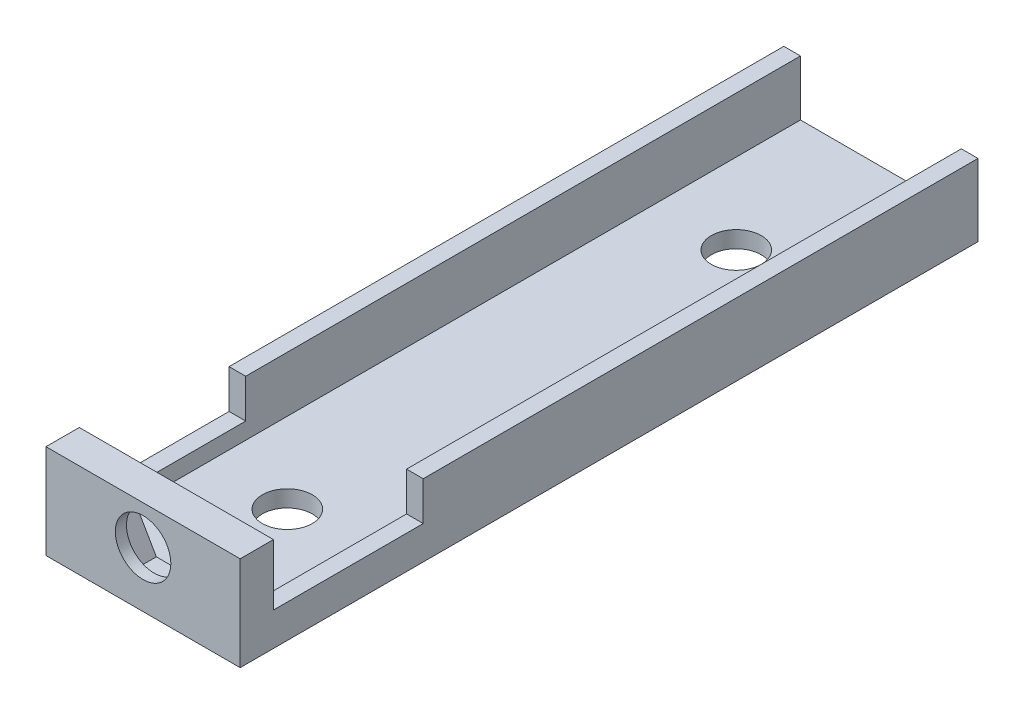
SolidWorks part; units mm, degrees
ref_plane "Front Plane" through (0, 0, 0) normal (0, 0, 1) x (1, 0, 0)
ref_plane "Top Plane" through (0, 0, 0) normal (0, 1, 0) x (1, 0, 0)
ref_plane "Right Plane" through (0, 0, 0) normal (1, 0, 0) x (0, 0, -1)
sketch "Sketch1" plane through (0, 0, 0) normal (0, 0, 1) x (1, 0, 0)
  line L0 (0, 0) -> (0, 13)
  line L1 (0, 13) -> (3, 13)
  line L2 (3, 13) -> (3, 3)
  line L3 (3, 3) -> (32, 3)
  line L4 (32, 3) -> (32, 13)
  line L5 (32, 13) -> (35, 13)
  line L6 (35, 13) -> (35, 0)
  line L7 (35, 0) -> (0, 0)
  line L8 (3, 3) -> (3, 0) construction
  dimension "D1" = 29
  dimension "D2" = 3
  dimension "D3" = 13
extrude "Boss-Extrude1" add sketch "Sketch1" along normal blind 100
sketch "Sketch2" plane through (0, 0, 100) normal (0, 0, 1) x (1, 0, 0)
  line L0 (3, 6) -> (3, 3)
  line L1 (3, 3) -> (3, 13) construction
  line L2 (3, 3) -> (32, 3)
  line L3 (32, 3) -> (32, 6)
  line L4 (32, 13) -> (32, 3) construction
  line L5 (32, 6) -> (35, 6)
  line L6 (35, 0) -> (35, 13) construction
  line L7 (35, 6) -> (35, 0)
  line L8 (35, 0) -> (0, 0)
  line L9 (0, 0) -> (0, 6)
  line L10 (0, 13) -> (0, 0) construction
  line L11 (0, 6) -> (3, 6)
  dimension "D1" = 3
extrude "Boss-Extrude2" add sketch "Sketch2" along normal blind 31
sketch "Sketch3" plane through (0, 0, 131) normal (0, 0, 1) x (1, 0, 0)
  line L0 (17.5, 10) -> (17.5, 17) construction
  line L1 (0, 0) -> (35, 0)
  line L2 (0, 0) -> (0, 17)
  line L3 (0, 17) -> (35, 17)
  line L4 (35, 0) -> (35, 17)
  line L5 (17.5, 10) -> (0, 10) construction
  line L6 (32, 3) -> (3, 3) construction
  line L8 (24.7169, 10) -> (21.1084, 16.25)
  line L9 (21.1084, 16.25) -> (13.8916, 16.25)
  line L10 (13.8916, 16.25) -> (10.2831, 10)
  line L11 (10.2831, 10) -> (13.8916, 3.75)
  line L12 (13.8916, 3.75) -> (21.1084, 3.75)
  line L13 (21.1084, 3.75) -> (24.7169, 10)
  circle A0 centre (17.5, 10) radius 5
  circle A1 centre (17.5, 10) radius 6.25 construction
  point P13 (24.7169, 9.5)
  point P21 (24.7169, 9.5)
  line M2 (3, 6) -> (0, 6)
  line M3 (0, 6) -> (0, 0)
  line M4 (0, 0) -> (35, 0)
  line M5 (35, 0) -> (35, 6)
  line M6 (35, 6) -> (32, 6)
  line M7 (32, 6) -> (32, 3)
  line M8 (32, 3) -> (3, 3)
  line M9 (3, 3) -> (3, 6)
  dimension "D1" = 10
  dimension "D2" = 17
  dimension "D3" = 12.5
extrude "Boss-Extrude3" add sketch "Sketch3" against normal blind 4 contours L4 L3 L2 L13 L12 L11 L10 L9 L8 M6 M2 M9 M8 M7 | M9 M2 M3 M4 M5 M6 M7 M8 region at (17.5, 1.939, 131) region at (0.377, 11.5, 131)
sketch "Sketch4" plane through (0, 3, 0) normal (0, 1, 0) x (1, 0, 0)
  line L0 (17.5, -26.075) -> (17.5, -107) construction
  line L1 (32, -127) -> (32, 0) construction
  line L2 (3, -127) -> (3, 0) construction
  line L4 (32, -127) -> (3, -127) construction
  circle A0 centre (17.5, -107) radius 4.5
  circle A1 centre (17.5, -26.075) radius 4.5
  dimension "D1" = 9
  dimension "D2" = 20
  dimension "D3" = 80.925
extrude "Cut-Extrude1" cut sketch "Sketch4" against normal through all
extrude "Boss-Extrude4" add sketch "Sketch3<4>" along normal blind 2 contours L4 L3 L2 L13 L12 L11 L10 L9 L8 M6 M2 M9 M8 M7 | M9 M2 M3 M4 M5 M6 M7 M8 | L12 L13 L8 L9 L10 L11 A0 region at (17.5, 1.939, 131) region at (0.377, 11.5, 131) region at (22.7473, 6.9705, 131)
sketch "Sketch3<4>" plane through (0, 0, 131) normal (0, 0, 1) x (1, 0, 0) same geometry as "Sketch3"
